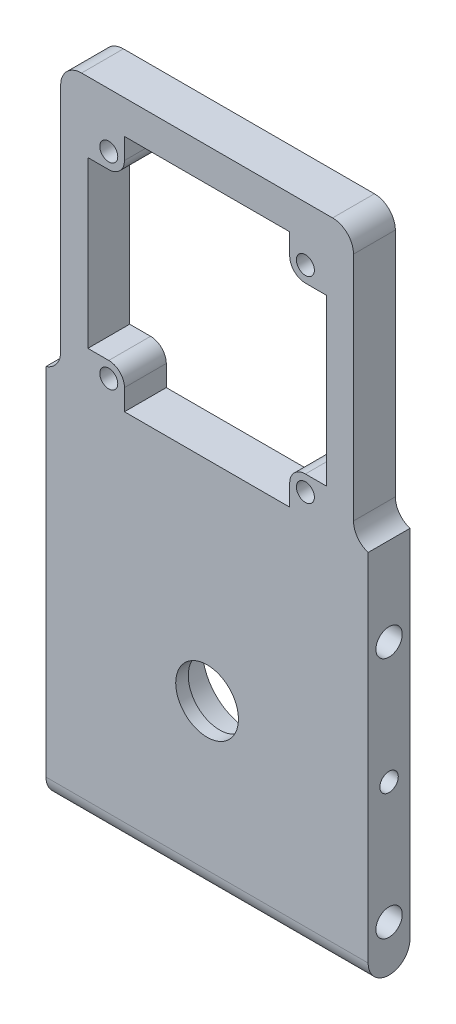
SolidWorks part; units mm, degrees
ref_plane "Ebene vorne" through (0, 0, 0) normal (0, 0, 1) x (1, 0, 0)
ref_plane "Ebene oben" through (0, 0, 0) normal (0, 1, 0) x (1, 0, 0)
ref_plane "Ebene rechts" through (0, 0, 0) normal (1, 0, 0) x (0, 0, -1)
sketch "Skizze1" plane through (0, 0, 0) normal (0, 0, 1) x (1, 0, 0)
  line L0 (0, 0) -> (0, -50000) construction
  line L1 (38.5, 50) -> (35, 50)
  line L2 (38.5, 50) -> (38.5, -40)
  line L3 (38.5, -40) -> (-38.5, -40)
  line L4 (-38.5, 50) -> (-38.5, -40)
  line L8 (-35, 50) -> (-35, 115)
  line L9 (-35, 115) -> (35, 115)
  line L10 (35, 50) -> (35, 115)
  line L11 (-35, 50) -> (-38.5, 50)
  point P0 (0, 0)
  dimension "D1" = 77
  dimension "D2" = 90
  dimension "D3" = 50
  dimension "D4" = 70
  dimension "D5" = 65
extrude "Aufsatz-Linear austragen1" add sketch "Skizze1" along normal mid plane 10
sketch "Skizze2" plane through (-38.5, 0, 0) normal (-1, 0, 0) x (0, 0, 1)
  line L0 (0, 0) -> (0, -50000) construction
  line L1 (-26.5378, 0) -> (44.9858, 0) construction
  circle A0 centre (0, 29) radius 3.15
  circle A1 centre (0, -29) radius 3.15
  dimension "D1" = 6.3
  dimension "D2" = 29
extrude "Schnitt-Linear austragen1" cut sketch "Skizze2" against normal through all
sketch "Skizze3" plane through (-38.5, 0, 0) normal (-1, 0, 0) x (0, 0, 1)
  circle A0 centre (0, 0) radius 2.2
  dimension "D1" = 4.4
extrude "Schnitt-Linear austragen2" cut sketch "Skizze3" against normal blind 15
cosmetic thread "Gewindedarstellung1" parameters "D2"=6
mirror "Spiegeln1" about plane through (0, 0, 0) normal (1, 0, 0) of "Schnitt-Linear austragen2"
cosmetic thread "Gewindedarstellung2" parameters "D2"=6
fillet "Verrundung2" radius 5 2 edges at (0, -40, -5) (0, -40, 5)
sketch "Skizze5" plane through (0, 0, 5) normal (0, 0, 1) x (1, 0, 0)
  line L0 (19.75, 102) -> (19.75, 107)
  line L1 (0, 51.3697) -> (0, -49948.6303) construction
  line L2 (-23.5, 98.25) -> (-28.5, 98.25)
  line L7 (-35, 50) -> (-38.5, 50) construction
  line L9 (-19.75, 107) -> (19.75, 107)
  line L10 (-28.5, 98.25) -> (-28.5, 58.75)
  line L11 (-19.75, 50) -> (19.75, 50)
  line L12 (28.5, 98.25) -> (28.5, 58.75)
  line L14 (-28.5, 78.5) -> (48.1659, 78.5) construction
  line L15 (-19.75, 102) -> (-19.75, 107)
  line L16 (-23.5, 55) -> (23.5, 55) construction
  line L17 (23.5, 98.25) -> (28.5, 98.25)
  line L18 (23.5, 58.75) -> (28.5, 58.75)
  line L19 (19.75, 55) -> (19.75, 50)
  line L20 (-23.5, 58.75) -> (-28.5, 58.75)
  line L21 (-19.75, 55) -> (-19.75, 50)
  line L22 (-23.5, 55) -> (-23.5, 102) construction
  line L23 (-23.5, 102) -> (23.5, 102) construction
  line L24 (23.5, 55) -> (23.5, 102) construction
  line L25 (-23.5, 55) -> (23.5, 102) construction
  line L26 (-23.5, 102) -> (23.5, 55) construction
  arc A0 (-23.5, 98.25) -> (-19.75, 102) centre (-23.5, 102) ccw
  arc A1 (19.75, 102) -> (23.5, 98.25) centre (23.5, 102) ccw
  arc A2 (23.5, 58.75) -> (19.75, 55) centre (23.5, 55) ccw
  arc A3 (-19.75, 55) -> (-23.5, 58.75) centre (-23.5, 55) ccw
  point P3 (0, 78.5)
  point P5 (0, 50)
  point P8 (0, 78.5)
  point P13 (0, 80)
  dimension "D3" = 7.5
  dimension "D2" = 57
  dimension "D4" = 57
  dimension "D5" = 47
extrude "Schnitt-Linear austragen3" cut sketch "Skizze5" against normal through all
hole_wizard "Ø4.3 (4.3) Durchmesser Bohrung1" positions "Skizze6" profile "Skizze7" hole size "Ø4.3" standard "ISO" end condition through all
sketch "Skizze6" plane through (0, 0, 5) normal (0, 0, 1) x (1, 0, 0)
  point P0 (-23.5, 102)
  point P3 (-23.5, 55)
  point P6 (23.5, 55)
  point P9 (23.5, 102)
sketch "Skizze7" plane through (-23.5, 102, 5) normal (1, 0, 0) x (0, -1, 0)
  line L0 (0, 0) -> (0, 10)
  line L1 (0, 10) -> (2.15, 10)
  line L2 (2.15, 10) -> (2.15, 0)
  line L5 (2.15, 0) -> (0, 0)
  line L11 (0, -6.35) -> (0, 107.95) construction
  dimension "Bohrerdurchmesser" = 4.3
  dimension "Bohrungstiefe" = 10
fillet "Verrundung3" radius 5 2 edges at (35, 115, 0) (-35, 115, 0)
fillet "Verrundung4" radius 5 2 edges at (35, 50, 0) (-35, 50, 0)
sketch "Skizze8" plane through (0, 0, -5) normal (0, 0, 1) x (1, 0, 0)
  circle A0 centre (0, 0) radius 11.1
  dimension "D1" = 22.2
extrude "Schnitt-Linear austragen4" cut sketch "Skizze8" along normal blind 7
sketch "Skizze9" plane through (0, 0, 2) normal (0, 0, -1) x (-1, 0, 0)
  circle A0 centre (0, 0) radius 7.5
  dimension "D1" = 15
extrude "Schnitt-Linear austragen5" cut sketch "Skizze9" against normal blind 10
